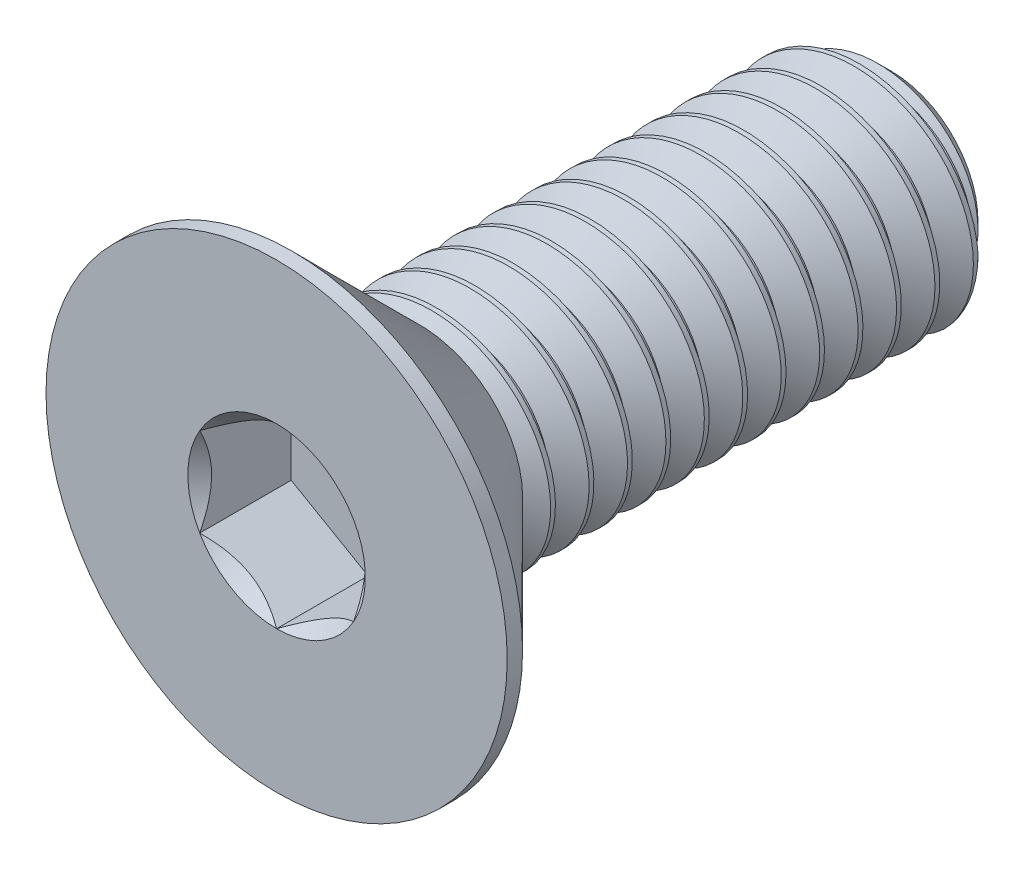
SolidWorks part; units mm, degrees
ref_plane "Front" through (0, 0, 0) normal (0, 0, 1) x (1, 0, 0)
ref_plane "Top" through (0, 0, 0) normal (0, 1, 0) x (1, 0, 0)
ref_plane "Right" through (0, 0, 0) normal (1, 0, 0) x (0, 0, -1)
sketch "Sketch1" plane through (0, 0, 0) normal (1, 0, 0) x (0, 0, -1)
  line L0 (0, 3) -> (0.2, 3) construction
  line L1 (0.2, 3) -> (1.7, 1.5) construction
  line L2 (0, 1.5) -> (8, 1.5)
  line L3 (8, 1.5) -> (8, 0)
  line L4 (8, 0) -> (0, 0)
  line L5 (0, 0) -> (0, 3) construction
  line L6 (0, 3) -> (0, -3) construction
  line L7 (8, 1.5) -> (8, -1.5) construction
  line L8 (0, -3) -> (0.2, -3) construction
  line L9 (0.2, -3) -> (1.7, -1.5) construction
  line L11 (0, 1.5) -> (0, 0)
  line L12 (1.7, 1.5) -> (1.7, 0) construction
revolve "Revolve1" add sketch "Sketch1" angle 360 mid plane about L4
sketch "Sketch3" plane through (0, 0, -8) normal (0, 0, -1) x (-1, 0, 0)
  circle A0 centre (0, 0) radius 1.5
curve "Helix/Spiral1" pitch 0.5 height 8 radius 1.5 centre (0, 0, -8) axis (0, 0, 1) start towards (0, 1, 0)
sketch "Sketch2" plane through (0, 0, 0) normal (1, 0, 0) x (0, 0, -1)
  line L0 (8, 1.5) -> (8.4375, 1.5)
  line L1 (8.4375, 1.5) -> (8.25, 1.1752)
  line L2 (8.25, 1.1752) -> (8.1875, 1.1752)
  line L3 (8.1875, 1.1752) -> (8, 1.5)
  line L4 (8.0938, 1.3376) -> (8.3438, 1.3376) construction
  dimension "D1" = 60
  dimension "D2" = 0.0625
  dimension "D3" = 0.25
chamfer "Chamfer1" distance 0.375 angle 45 1 edges at (0, 1.5, -8)
sweep "Cut-Sweep1" cut profiles "Sketch2" path "Helix/Spiral1" align with end faces yes
sketch "Sketch7" plane through (0, 0, 0) normal (1, 0, 0) x (0, 0, -1)
  line L0 (0, 3) -> (0.2, 3) construction
  line L1 (0.2, 3) -> (1.7, 1.5) construction
  line L2 (0, 3) -> (0.2, 3)
  line L3 (0.2, 3) -> (1.7, 1.5)
  line L4 (1.7, 1.5) -> (1.7, 0) construction
  line L5 (1.7, 1.5) -> (1.7, 0)
  line L7 (0, 0) -> (0, 3) construction
  line L8 (0, 0) -> (0, 3)
  line L9 (0, 0) -> (1.7, 0)
  line L10 (3.3, 0) -> (-3.3, 0) construction
revolve "Revolve2" add sketch "Sketch7" angle 360 mid plane about L9
ref_plane "Plane1" through (0, 0, -1.7) normal (0, 0, 1) x (1, 0, 0)
sketch "Sketch8" plane through (0, 0, -1.7) normal (0, 0, 1) x (1, 0, 0)
  circle A0 centre (0, 0) radius 1.5
extrude "Boss-Extrude1" add sketch "Sketch8" against normal through all draft 45
sketch "Sketch5" plane through (0, 0, 0) normal (0, 0, 1) x (1, 0, 0)
  line L1 (1, -0.5774) -> (1, 0.5774)
  line L2 (1, 0.5774) -> (0, 1.1547)
  line L3 (0, 1.1547) -> (-1, 0.5774)
  line L4 (-1, 0.5774) -> (-1, -0.5774)
  line L5 (-1, -0.5774) -> (0, -1.1547)
  line L6 (0, -1.1547) -> (1, -0.5774)
  circle A0 centre (0, 0) radius 1 construction
  dimension "Hex" = 2
extrude "Cut-Extrude2" cut sketch "Sketch5" against normal blind 1.19
sketch "Sketch6" plane through (0, 0, 0) normal (0, 0, 1) x (1, 0, 0)
  circle A0 centre (0, 0) radius 1.1547
extrude "Cut-Extrude3" cut sketch "Sketch6" against normal blind 1.19 draft 45
sketch "Sketch9" [suppressed] plane through (0, 0, -1.5) normal (0, 0, 1) x (1, 0, 0)
  circle A1 centre (0, 0) radius 1.25
  circle A2 centre (0, 0) radius 1.25
  point P0 (0, 1.25)
  dimension "D1" = 0
extrude "Boss-Extrude2" [suppressed] add sketch "Sketch9" against normal offset from surface (3.5 mm away) 26 up to face at (0, 1.125, -8)
fillet "Fillet1" [suppressed] radius 0.3
sketch "Sketch10" plane through (0, 0, 0) normal (1, 0, 0) x (0, 0, -1)
  line L0 (8, 1.5) -> (8, -1.5) construction
  point P0 (7.25, -1.5)
  dimension "D1" = 0.75
equation "\"D3@Helix/Spiral1\" = \"Lg@Sketch1\""
equation "\"D2@Sketch2\" = \"D4@Helix/Spiral1\" * .125"
equation "\"D3@Sketch2\" = \"D4@Helix/Spiral1\" * .5"
equation "\"D1@Chamfer1\" = \"D4@Helix/Spiral1\" * .75"
equation "\"D1@Cut-Extrude2\" = \"Head Ht@Sketch1\" * .7"
equation "\"D1@Sketch10\" = \"D4@Helix/Spiral1\" * 1.5"
equation "\"D1@Cut-Extrude3\" = \"D1@Cut-Extrude2\""
equation "\"D1@Fillet1\" = \"Dia@Sketch1\" * .1"
